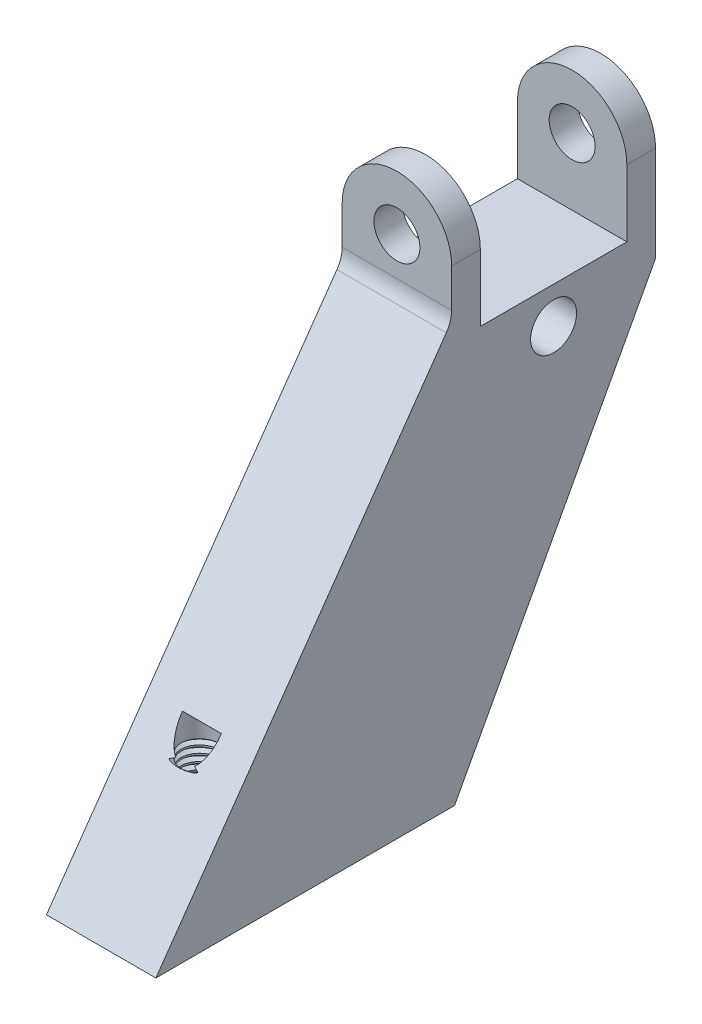
SolidWorks part; units mm, degrees
ref_plane "Front Plane" through (0, 0, 0) normal (0, 0, 1) x (1, 0, 0)
ref_plane "Top Plane" through (0, 0, 0) normal (0, 1, 0) x (1, 0, 0)
ref_plane "Right Plane" through (0, 0, 0) normal (1, 0, 0) x (0, 0, -1)
sketch "Sketch6" plane through (0, 3.4314, 0) normal (0, 1, 0) x (-1, 0, 0)
  line L0 (-13.5144, 0) -> (5.5356, 0)
  line L5 (-7.9894, 155.54) -> (0.0106, 155.54) construction
  line L8 (5.5356, 0) -> (5.5356, 133.908)
  line L9 (5.5356, 133.908) -> (-13.5144, 133.908)
  line L10 (-13.5144, 0) -> (-13.5144, 133.908)
  line L17 (-7.9894, 155.54) -> (0.0106, 155.54) construction
  line L18 (-3.9894, 155.54) -> (-3.9894, 0) construction
  dimension "D1" = 19.05
sketch3d "3DSketch1" [suppressed]
  circle A0 centre (4.1661, 92.3902, 4.7625) radius 4 construction
  circle A1 centre (4.1661, 92.3902, 4.7625) radius 4
  circle A2 centre (4.1661, 92.3902, 30.1625) radius 4 construction
  circle A3 centre (4.1661, 92.3902, 30.1625) radius 4
  point P2 (4.1661, 92.3902, 8.7625)
  point P4 (4.1661, 92.3902, 8.7625)
  point P7 (4.1661, 92.3902, 34.1625)
  point P9 (4.1661, 92.3902, 34.1625)
extrude "Boss-Extrude5" add sketch "Sketch6" along normal blind 101.6
sketch "Sketch9" plane through (0, 0, 0) normal (0, 0, -1) x (-1, 0, 0)
  line L1 (-13.5144, 105.0314) -> (6.0586, 105.0314)
  line L2 (-13.5144, 105.0314) -> (-13.5144, 87.861)
  line L3 (-13.5144, 87.861) -> (6.0586, 87.861)
  line L12 (6.0586, 105.0314) -> (6.0586, 87.861)
extrude "Cut-Extrude5" [suppressed] cut sketch "Sketch9" against normal through all
sketch "Sketch10" plane through (13.5144, 0, 0) normal (1, 0, 0) x (0, 0, -1)
  line L0 (-87, 3.4314) -> (-167.5984, 3.4314)
  line L1 (-133.908, 3.4314) -> (0, 3.4314) construction
  line L2 (-167.5984, 3.4314) -> (-168.5558, 132.8824)
  line L3 (-168.5558, 132.8824) -> (-35.5045, 117.0228)
  line L4 (-35.5045, 117.0228) -> (-35.5045, 78.3573)
  line L5 (-36.4274, 75.4376) -> (-87, 3.4314)
  line L6 (-35, 3.4314) -> (7.4334, 3.4314)
  line L7 (7.4334, 3.4314) -> (7.4334, 68.4314)
  line L8 (7.4334, 68.4314) -> (0, 68.4314)
  line L9 (0, 68.4314) -> (-35, 3.4314)
  line L10 (0, 105.0314) -> (0, 3.4314) construction
  line L12 (-30.5045, 96.7069) -> (-5, 96.7069)
  line L13 (-30.5045, 96.7069) -> (-30.5045, 73.4314)
  line L14 (-30.5045, 73.4314) -> (-5, 73.4314)
  line L15 (-5, 96.7069) -> (-5, 73.4314)
  arc A0 (-35.5045, 78.3573) -> (-36.4274, 75.4376) centre (-40.5845, 78.3573) cw
  point P22 (-30.5045, 85.0692)
  dimension "D8" = 5.08
  dimension "D1" = 5
  dimension "D2" = 5
  dimension "D3" = 65
  dimension "D4" = 35
  dimension "D5" = 52
  dimension "D6" = 25.5045
  dimension "D7" = 70
extrude "Cut-Extrude6" cut sketch "Sketch10" against normal through all
sketch "Sketch12" plane through (0, 0, 35.5045) normal (0, 0, 1) x (1, 0, 0)
  line L0 (3.9894, 3.4314) -> (3.9894, 85.0528) construction
  line L1 (7.9894, 3.4314) -> (-0.0106, 3.4314) construction
  line L2 (-5.5356, 85.0528) -> (13.5144, 85.0528) construction
  line L3 (-5.5356, 78.3573) -> (-5.5356, 105.0314) construction
  line L4 (13.5144, 78.3573) -> (13.5144, 105.0314) construction
  line L5 (13.5144, 85.0528) -> (39.9433, 85.0528)
  line L6 (39.9433, 85.0528) -> (39.9433, 114.8081)
  line L7 (39.9433, 114.8081) -> (-16.1264, 114.8081)
  line L8 (-16.1264, 114.8081) -> (-16.1264, 85.0528)
  line L9 (-16.1264, 85.0528) -> (-5.5356, 85.0528)
  circle A0 centre (3.9894, 85.0528) radius 4
  arc A1 (13.5144, 85.0528) -> (-5.5356, 85.0528) centre (3.9894, 85.0528) ccw
  dimension "D2" = 8
  dimension "D1" = 81.6214
extrude "Cut-Extrude7" cut sketch "Sketch12" against normal through all
sketch "Sketch13" plane through (0, 3.4314, 0) normal (0, -1, 0) x (1, 0, 0)
  line L0 (3.9894, 87) -> (3.9894, 69.5) construction
  line L1 (-5.5356, 87) -> (13.5144, 87) construction
  line L2 (3.9894, 155.54) -> (3.9894, 0) construction
  line L3 (3.9894, 69.5) -> (3.9894, 42.5) construction
  dimension "D1" = 17.5
  dimension "D2" = 27
sketch "Sketch14" plane through (0, 3.4314, 0) normal (0, -1, 0) x (1, 0, 0)
  circle A0 centre (3.9894, 69.5) radius 3.4
  circle A1 centre (3.9894, 42.5) radius 3.4
  dimension "D1" = 6.8
extrude "Cut-Extrude8" cut sketch "Sketch14" against normal blind 25
thread "Thread1" pitch 1.25 method cut profile "Thread Profile1" start angle 0, offset 0, length 20, pitch 1.25, diameter 6.8
ref_plane "Plane1" through (7.3894, 3.4314, 42.5) normal (0, 0, 1) x (1, 0, 0)
sketch "Thread Profile1" plane through (7.3894, 3.4314, 42.5) normal (0, 0, 1) x (1, 0, 0)
  line L0 (0, 0) -> (0, 1.25) construction
  line L1 (0, 0) -> (0.6766, 0.3906)
  line L2 (0.6766, 0.3906) -> (0.6766, 0.5469)
  line L3 (0.6766, 0.5469) -> (0, 0.9375)
  line L4 (0.6766, 0.4687) -> (0, 0.4687) construction
  line L11 (0, 0) -> (0, 0.9375)
  point P2 (0, 0)
  dimension "Pitch" = 1.25
  dimension "Profile_Angle" = 60
  dimension "Profile_Land" = 0.1562
  dimension "Profile_Height" = 0.6766
thread "Thread2" pitch 1.25 method cut profile "Thread Profile2" start angle 0, offset 0, length 20, pitch 1.25, diameter 6.8
ref_plane "Plane2" through (7.3894, 3.4314, 69.5) normal (0, 0, 1) x (1, 0, 0)
sketch "Thread Profile2" plane through (7.3894, 3.4314, 69.5) normal (0, 0, 1) x (1, 0, 0)
  line L0 (0, 0) -> (0, 1.25) construction
  line L1 (0, 0) -> (0.6766, 0.3906)
  line L2 (0.6766, 0.3906) -> (0.6766, 0.5469)
  line L3 (0.6766, 0.5469) -> (0, 0.9375)
  line L4 (0.6766, 0.4687) -> (0, 0.4687) construction
  line L11 (0, 0) -> (0, 0.9375)
  point P2 (0, 0)
  dimension "Pitch" = 1.25
  dimension "Profile_Angle" = 60
  dimension "Profile_Land" = 0.1562
  dimension "Profile_Height" = 0.6766
sketch "Sketch19" plane through (13.5144, 0, 0) normal (1, 0, 0) x (0, 0, -1)
  line L0 (-17.7522, 73.4314) -> (-17.7522, 67.0814) construction
  line L1 (-30.5045, 73.4314) -> (-5, 73.4314) construction
  circle A0 centre (-17.7522, 67.0814) radius 4
  dimension "D1" = 6.35
  dimension "D2" = 8
extrude "Cut-Extrude9" cut sketch "Sketch19" against normal through all
